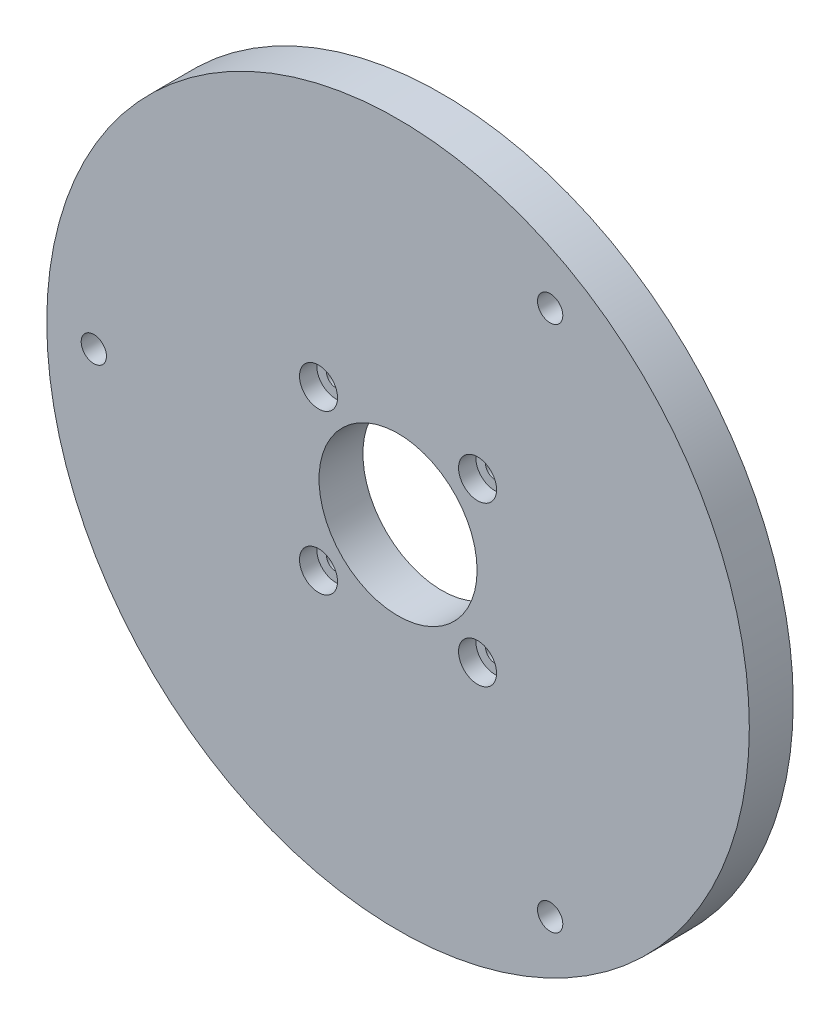
SolidWorks part; units mm, degrees
material "Acrylic (Medium-high impact)"
ref_plane "Front Plane" through (0, 0, 0) normal (0, 0, 1) x (1, 0, 0)
ref_plane "Top Plane" through (0, 0, 0) normal (0, 1, 0) x (1, 0, 0)
ref_plane "Right Plane" through (0, 0, 0) normal (1, 0, 0) x (0, 0, -1)
sketch "Sketch1" plane through (0, 0, 0) normal (0, 0, 1) x (1, 0, 0)
  circle A0 centre (0, 0) radius 50.8
  dimension "D1" = 101.6
extrude "Boss-Extrude1" add sketch "Sketch1" along normal blind 6.35
sketch "Sketch2" plane through (0, 0, 6.35) normal (0, 0, 1) x (1, 0, 0)
  circle A0 centre (0, 0) radius 11.43
  dimension "D1" = 22.86
extrude "Cut-Extrude1" cut sketch "Sketch2" against normal through all
hole_wizard "CBORE for M2.5 SHCS1" positions "Sketch3" profile "Sketch5" counterbore size "M2.5" standard "ANSI Metric"
sketch "Sketch3" plane through (0, 0, 6.35) normal (0, 0, 1) x (1, 0, 0)
  line L1 (-11.5, -11.5) -> (11.5, -11.5)
  line L2 (-11.5, -11.5) -> (-11.5, 11.5)
  line L3 (-11.5, 11.5) -> (11.5, 11.5)
  line L4 (11.5, -11.5) -> (11.5, 11.5)
  line L5 (-11.5, -11.5) -> (11.5, 11.5) construction
  line L6 (-11.5, 11.5) -> (11.5, -11.5) construction
  point P1 (0, 0)
  point P2 (11.5, 11.5)
  point P59 (-11.5, -11.5)
  point P60 (-11.5, 11.5)
  point P61 (11.5, -11.5)
  dimension "D1" = 23
sketch "Sketch5" plane through (0, 0, 6.35) normal (1, 0, 0) x (0, -1, 0)
  line L0 (0, 0) -> (0, 10.9712)
  line L1 (0, 10.9712) -> (1.35, 10.16)
  line L2 (1.35, 10.16) -> (1.35, 2.5)
  line L3 (1.35, 2.5) -> (2.75, 2.5)
  line L4 (2.75, 2.5) -> (2.75, 0)
  line L5 (2.75, 0) -> (0, 0)
  line L10 (0, 10.9712) -> (-1.35, 10.16) construction
  line L11 (0, -6.35) -> (0, 107.95) construction
  dimension "Hole Dia." = 2.7
  dimension "Hole Depth" = 10.16
  dimension "C'Bore Dia." = 5.5
  dimension "C'Bore Depth" = 2.5
  dimension "Drill Angle" = 118
hole_wizard "#6 Clearance Hole1" positions "Sketch7" profile "Sketch9" hole size "#6" standard "ANSI Inch"
sketch "Sketch7" plane through (0, 0, 6.35) normal (0, 0, 1) x (1, 0, 0)
  line L1 (21.997, -38.1) -> (21.997, 38.1)
  line L2 (21.997, 38.1) -> (-43.9941, 0)
  line L3 (-43.9941, 0) -> (21.997, -38.1)
  line L6 (0, 0) -> (-50.8, 0) construction
  circle A0 centre (0, 0) radius 21.997 construction
  circle A1 centre (0, 0) radius 50.8 construction
  point P3 (21.997, -38.1)
  point P4 (21.997, 38.1)
  point P5 (-43.9941, 0)
  point P21 (0, 0)
  dimension "D1" = 76.2
sketch "Sketch9" plane through (-43.9941, 0, 6.35) normal (1, 0, 0) x (0, -1, 0)
  line L0 (0, 0) -> (0, 11.2589)
  line L1 (0, 11.2589) -> (1.8288, 10.16)
  line L2 (1.8288, 10.16) -> (1.8288, 0)
  line L5 (1.8288, 0) -> (0, 0)
  line L10 (0, 11.2589) -> (-1.8288, 10.16) construction
  line L11 (0, -6.35) -> (0, 107.95) construction
  dimension "Hole Dia." = 3.6576
  dimension "Hole Depth" = 10.16
  dimension "Drill Angle" = 118
